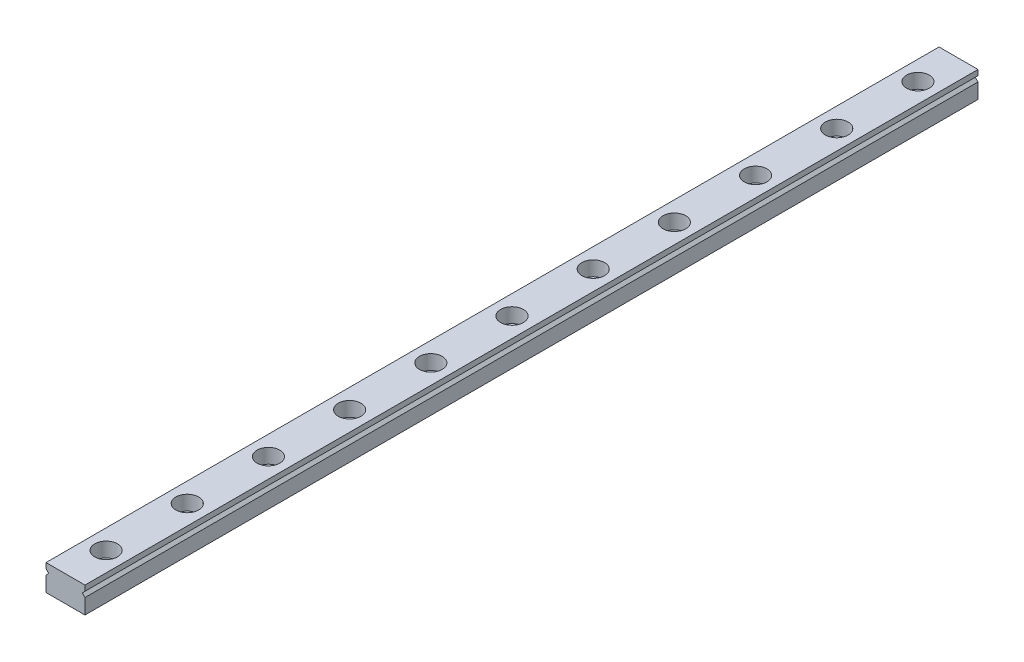
SolidWorks part; units mm, degrees
note: The reader was unsure of these and kept them because the rebuilt part matched: shared geometry of "Sketch2<3>".
material "Stainless Steel (ferritic)"
ref_plane "Front Plane" through (0, 0, 0) normal (0, 0, 1) x (1, 0, 0)
ref_plane "Top Plane" through (0, 0, 0) normal (0, 1, 0) x (1, 0, 0)
ref_plane "Right Plane" through (0, 0, 0) normal (1, 0, 0) x (0, 0, -1)
sketch "Sketch1" plane through (0, 0, 0) normal (0, 0, 1) x (1, 0, 0)
  line L20 (6, -3) -> (6, 1.6667)
  line L21 (6, 1.6667) -> (5.1667, 2.5)
  line L22 (5.1667, 2.5) -> (6, 3.3333)
  line L23 (6, 3.3333) -> (6, 5)
  line L24 (6, 5) -> (-6, 5)
  line L25 (-6, 5) -> (-6, 3.3333)
  line L26 (-6, 3.3333) -> (-5.1667, 2.5)
  line L27 (-5.1667, 2.5) -> (-6, 1.6667)
  line L28 (-6, 1.6667) -> (-6, -3)
  line L29 (-6, -3) -> (6, -3)
extrude "Boss-Extrude1" add sketch "Sketch1" along normal blind 275
sketch "Sketch2" plane through (0, 5, 0) normal (0, 1, 0) x (1, 0, 0)
  line L0 (0, 0) -> (0, -12.5)
  line L1 (0, -262.5) -> (0, -275)
  line L2 (-6, -275) -> (-6, 0)
  line L3 (-6, -137.5) -> (19.33, -137.5)
  line L4 (6, 0) -> (-6, 0)
  line L5 (-6, 0) -> (-6, -275)
  line L6 (-6, -275) -> (6, -275)
  line L7 (6, -275) -> (6, 0)
  line L8 (6, 0) -> (-6, 0)
  line L9 (-6, 0) -> (-6, -275)
  line L10 (-6, -275) -> (6, -275)
  line L11 (6, -275) -> (6, 0)
  circle A0 centre (0, -12.5) radius 3.5
  circle A1 centre (0, -37.5) radius 3.5
  circle A2 centre (0, -62.5) radius 3.5
  circle A3 centre (0, -87.5) radius 3.5
  circle A4 centre (0, -112.5) radius 3.5
  circle A5 centre (0, -137.5) radius 3.5
  circle A6 centre (0, -162.5) radius 3.5
  circle A7 centre (0, -187.5) radius 3.5
  circle A8 centre (0, -212.5) radius 3.5
  circle A9 centre (0, -237.5) radius 3.5
  circle A10 centre (0, -262.5) radius 3.5
  circle A11 centre (0, -12.5) radius 2.5
  circle A12 centre (0, -37.5) radius 2.5
  circle A13 centre (0, -62.5) radius 2.5
  circle A14 centre (0, -87.5) radius 2.5
  circle A15 centre (0, -112.5) radius 2.5
  circle A16 centre (0, -137.5) radius 2.5
  circle A17 centre (0, -162.5) radius 2.5
  circle A18 centre (0, -187.5) radius 2.5
  circle A19 centre (0, -212.5) radius 2.5
  circle A20 centre (0, -237.5) radius 2.5
  circle A21 centre (0, -262.5) radius 2.5
  dimension "D2" = 11
  dimension "D3" = 1
  dimension "D1" = 0
extrude "Cut-Extrude1" cut sketch "Sketch2" against normal through all
extrude "Cut-Extrude2" cut sketch "Sketch2<3>" against normal blind 4.5
sketch "Sketch2<3>" plane through (0, 5, 0) normal (0, 1, 0) x (1, 0, 0) same geometry as "Sketch2"
sketch "Sketch3" plane through (0, 5, 0) normal (0, 1, 0) x (1, 0, 0)
  line L0 (3.5, -137.5) -> (-21.5, -137.5)
  circle A0 centre (0, -137.5) radius 3.5 construction
